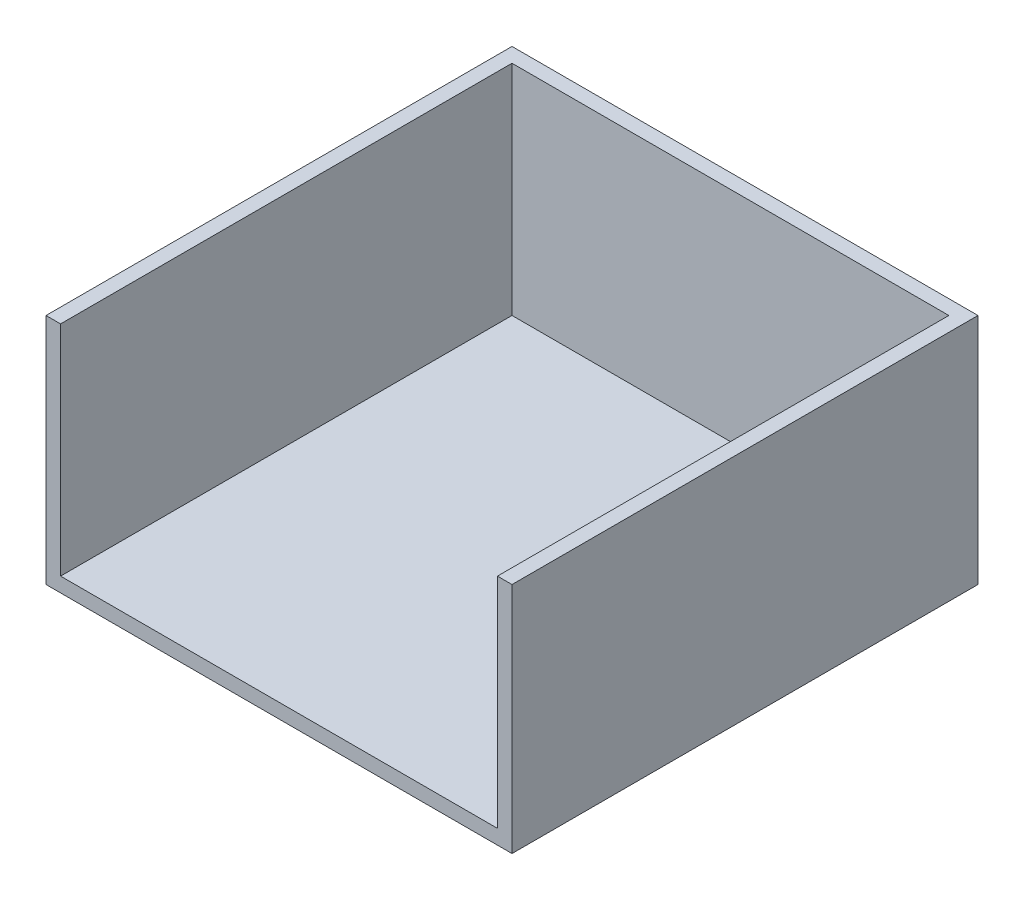
SolidWorks part; units mm, degrees
ref_plane "Front Plane" through (0, 0, 0) normal (0, 0, 1) x (1, 0, 0)
ref_plane "Top Plane" through (0, 0, 0) normal (0, 1, 0) x (1, 0, 0)
ref_plane "Right Plane" through (0, 0, 0) normal (1, 0, 0) x (0, 0, -1)
sketch "Sketch1" plane through (0, 0, 0) normal (0, 0, 1) x (1, 0, 0)
  line L1 (-152.4, -76.2) -> (152.4, -76.2)
  line L2 (-152.4, -76.2) -> (-152.4, 76.2)
  line L3 (-152.4, 76.2) -> (152.4, 76.2)
  line L4 (152.4, -76.2) -> (152.4, 76.2)
  line L5 (-152.4, -76.2) -> (152.4, 76.2) construction
  line L6 (-152.4, 76.2) -> (152.4, -76.2) construction
  point P0 (0, 0)
  dimension "D1" = 304.8
  dimension "D2" = 152.4
extrude "Boss-Extrude1" add sketch "Sketch1" along normal blind 304.8
shell "Shell1" thickness 9.525 removed face at (0, 0, 304.8) removed face at (0, 76.2, 152.4)
